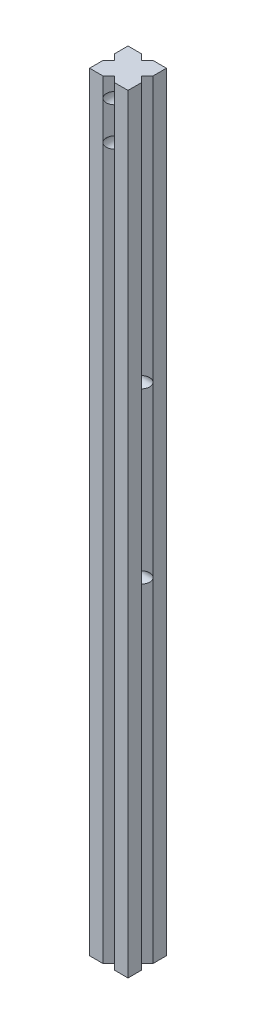
SolidWorks part; units mm, degrees
ref_plane "Front" through (0, 0, 0) normal (0, 0, 1) x (1, 0, 0)
ref_plane "Top" through (0, 0, 0) normal (0, 1, 0) x (1, 0, 0)
ref_plane "Right" through (0, 0, 0) normal (1, 0, 0) x (0, 0, -1)
sketch "Skizze1" plane through (0, 0, 0) normal (0, 1, 0) x (1, 0, 0)
  line L0 (0, 0) -> (0, 20)
  line L1 (0, 20) -> (20, 20)
  line L2 (20, 20) -> (20, 0)
  line L3 (20, 0) -> (0, 0)
  dimension "D1" = 20
extrude "Aufsatz-Linear austragen1" add sketch "Skizze1" along normal blind 400
sketch "Skizze2" plane through (0, 400, 0) normal (0, 1, 0) x (1, 0, 0)
  line L0 (20, 20) -> (0, 20) construction
  line L1 (20, 0) -> (20, 20) construction
  line L4 (0, 20) -> (0, 0) construction
  line L15 (10, 20) -> (10, 0) construction
  line L16 (0, 10) -> (20, 10) construction
  line L17 (7, 20) -> (10, 17)
  line L18 (13, 20) -> (10, 17)
  line L19 (10, 10) -> (20, 20) construction
  line L20 (7, 20) -> (13, 20)
  line L21 (20, 13) -> (17, 10)
  line L22 (20, 7) -> (17, 10)
  line L23 (20, 7) -> (20, 13)
  line L24 (0, 7) -> (0, 13)
  line L25 (0, 7) -> (3, 10)
  line L26 (0, 13) -> (3, 10)
  line L27 (7, 0) -> (13, 0)
  line L28 (13, 0) -> (10, 3)
  line L29 (7, 0) -> (10, 3)
  line L30 (0, 0) -> (20, 0) construction
  dimension "D1" = 3
  dimension "D2" = 3
extrude "Schnitt-Linear austragen1" cut sketch "Skizze2" against normal through all
sketch "Sketch1" plane through (20, 0, 0) normal (1, 0, 0) x (0, 0, -1)
  line L0 (10, 0) -> (10, 400) construction
  line L1 (0, 400) -> (7, 400) construction
  circle A0 centre (10, 262) radius 3
  circle A1 centre (10, 174) radius 3
  dimension "D1" = 6
  dimension "D2" = 6
  dimension "D3" = 138
  dimension "D4" = 88
extrude "Cut-Extrude1" cut sketch "Sketch1" against normal blind 20
sketch "Sketch2" plane through (0, 0, 0) normal (0, 0, 1) x (1, 0, 0)
  line L0 (10, 0) -> (10, 400) construction
  line L1 (0, 400) -> (7, 400) construction
  circle A0 centre (10, 390) radius 3
  circle A1 centre (10, 370) radius 3
  dimension "D1" = 6
  dimension "D2" = 10
  dimension "D3" = 20
extrude "Cut-Extrude2" cut sketch "Sketch2" against normal blind 20
